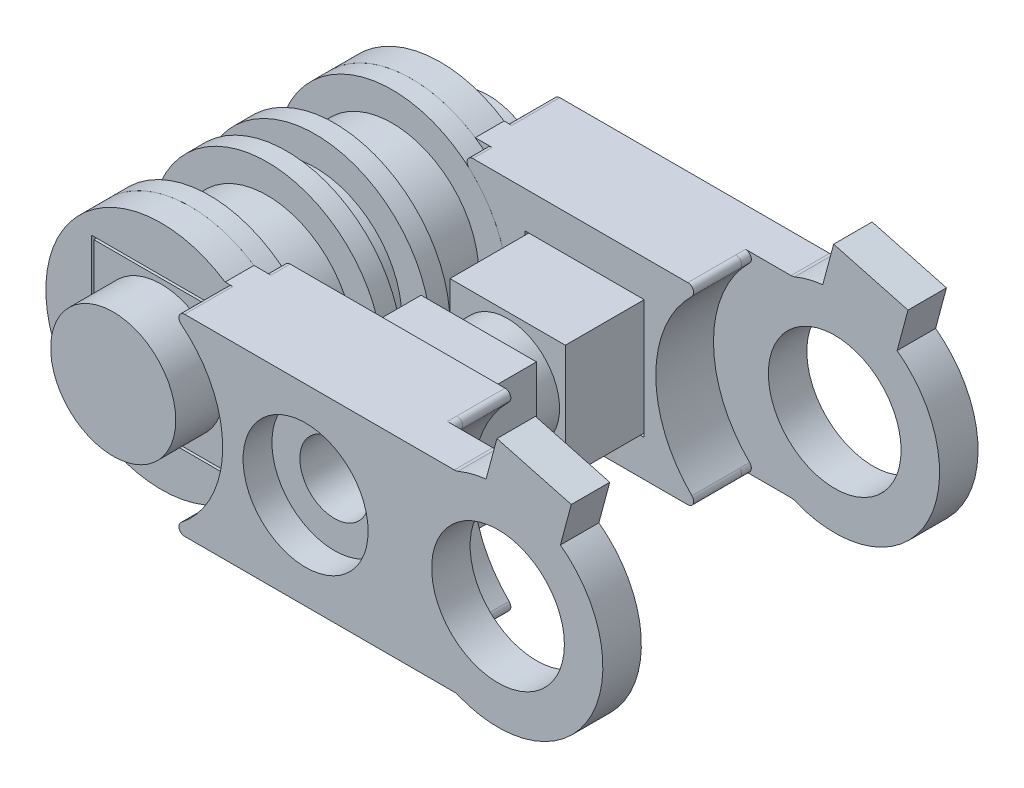
SolidWorks part; units mm, degrees
ref_plane "正面" through (0, 0, 0) normal (0, 0, 1) x (1, 0, 0)
ref_plane "平面" through (0, 0, 0) normal (0, 1, 0) x (1, 0, 0)
ref_plane "右側面" through (0, 0, 0) normal (1, 0, 0) x (0, 0, -1)
sketch "ｽｹｯﾁ1" plane through (0, 0, 0) normal (0, 0, 1) x (1, 0, 0)
  circle A0 centre (0, 0) radius 4.5
  dimension "D1" = 9
extrude "ﾎﾞｽ - 押し出し1" add sketch "ｽｹｯﾁ1" along normal blind 3
sketch "ｽｹｯﾁ2" plane through (0, 0, 0) normal (0, 0, -1) x (-1, 0, 0)
  circle A0 centre (0, 0) radius 6
  dimension "D1" = 12
extrude "ﾎﾞｽ - 押し出し2" add sketch "ｽｹｯﾁ2" along normal blind 1
sketch "ｽｹｯﾁ3" plane through (0, 0, -1) normal (0, 0, -1) x (-1, 0, 0)
  circle A0 centre (0, 0) radius 4.5 construction
  circle A1 centre (0, 0) radius 4.5
extrude "ﾎﾞｽ - 押し出し3" add sketch "ｽｹｯﾁ3" along normal blind 1.5
sketch "ｽｹｯﾁ4" plane through (0, 0, -2.5) normal (0, 0, -1) x (-1, 0, 0)
  circle A1 centre (0, 0) radius 6
  circle A2 centre (0, 0) radius 6
  dimension "D1" = 0
extrude "ﾎﾞｽ - 押し出し4" add sketch "ｽｹｯﾁ4" along normal blind 1
sketch "ｽｹｯﾁ5" plane through (0, 0, -3.5) normal (0, 0, -1) x (-1, 0, 0)
  circle A0 centre (0, 0) radius 4.5 construction
  circle A1 centre (0, 0) radius 4.5
extrude "ﾎﾞｽ - 押し出し5" add sketch "ｽｹｯﾁ5" along normal blind 3
sketch "ｽｹｯﾁ6" plane through (0, 0, -6.5) normal (0, 0, -1) x (-1, 0, 0)
  circle A1 centre (0, 0) radius 6
  circle A2 centre (0, 0) radius 6
  dimension "D1" = 0
extrude "ﾎﾞｽ - 押し出し6" add sketch "ｽｹｯﾁ6" along normal blind 1
sketch "ｽｹｯﾁ7" plane through (0, 0, 3) normal (0, 0, 1) x (1, 0, 0)
  circle A1 centre (0, 0) radius 6
  circle A2 centre (0, 0) radius 6
  dimension "D1" = 0
extrude "ﾎﾞｽ - 押し出し7" add sketch "ｽｹｯﾁ7" along normal blind 1
sketch "ｽｹｯﾁ10" plane through (0, 0, 4) normal (0, 0, 1) x (1, 0, 0)
  line L1 (3.5, -3.5) -> (-3.5, -3.5)
  line L2 (3.5, -3.5) -> (3.5, 3.5)
  line L3 (3.5, 3.5) -> (-3.5, 3.5)
  line L4 (-3.5, -3.5) -> (-3.5, 3.5)
  line L5 (3.5, -3.5) -> (-3.5, 3.5) construction
  line L6 (3.5, 3.5) -> (-3.5, -3.5) construction
  point P0 (0, 0)
  dimension "D1" = 7
  dimension "D2" = 7
extrude "ﾎﾞｽ - 押し出し10" add sketch "ｽｹｯﾁ10" along normal blind 1.5
sketch "ｽｹｯﾁ11" plane through (0, 0, 5.5) normal (0, 0, 1) x (1, 0, 0)
  circle A0 centre (0, 0) radius 3.25
  dimension "D1" = 6.5
extrude "ﾎﾞｽ - 押し出し11" add sketch "ｽｹｯﾁ11" along normal blind 2.5
ref_plane "平面1" through (0, 0, -1.75) normal (0, 0, 1) x (1, 0, 0)
mirror "ﾐﾗｰ1" about plane through (0, 0, -1.75) normal (0, 0, 1) of "ﾎﾞｽ - 押し出し11", "ﾎﾞｽ - 押し出し10"
sketch "ｽｹｯﾁ12" plane through (0, 0, 4) normal (0, 0, 1) x (1, 0, 0)
  line L0 (0, 0) -> (20, 0) construction
  line L1 (3.3166, 5) -> (16.1672, 5)
  line L3 (16.1672, -5) -> (3.3166, -5)
  line L8 (3.64, -3.64) -> (3.64, 3.64)
  line L9 (-3.64, -3.64) -> (3.64, -3.64)
  line L10 (-3.64, 3.64) -> (-3.64, -3.64)
  line L11 (3.64, 3.64) -> (-3.64, 3.64)
  line L12 (3.64, -3.64) -> (3.64, 3.64)
  line L13 (-3.64, -3.64) -> (3.64, -3.64)
  line L14 (-3.64, 3.64) -> (-3.64, -3.64)
  line L15 (3.64, 3.64) -> (-3.64, 3.64)
  circle A0 centre (0, 0) radius 6 construction
  circle A1 centre (20, 0) radius 3.45 construction
  arc A2 (3.3166, 5) -> (3.3166, -5) centre (0, 0) ccw
  circle A3 centre (20, 0) radius 5.45 construction
  circle A4 centre (20, 0) radius 6.3 construction
  arc A5 (16.1672, 5) -> (16.1672, -5) centre (20, 0) ccw
  circle A6 centre (20, 0) radius 6 construction
  circle A7 centre (0, 0) radius 6 construction
  circle A8 centre (20, 0) radius 3.25 construction
  circle A9 centre (0, 0) radius 3.25 construction
  dimension "D3" = 20
  dimension "D6" = 0.3
  dimension "D2" = 5
  dimension "D7" = 5
  dimension "D4" = 0.2
  dimension "D5" = 2
  dimension "D1" = 0.14
extrude "ﾎﾞｽ - 押し出し12" add sketch "ｽｹｯﾁ12" along normal blind 1.5 separate body
sketch "ｽｹｯﾁ13" plane through (0, 0, 5.5) normal (0, 0, 1) x (1, 0, 0)
  line L6 (16.1672, 5) -> (3.3166, 5) construction
  line L9 (16.1672, 5) -> (3.3166, 5) construction
  line L10 (15.3664, 5) -> (3.7135, 5)
  line L11 (15.3664, -5) -> (3.7135, -5)
  circle A1 centre (0, 0) radius 3.25 construction
  arc A7 (16.1672, 5) -> (16.1672, -5) centre (20, 0) ccw construction
  arc A8 (15.577, 4.4864) -> (15.577, -4.4864) centre (20, 0) ccw
  circle A10 centre (0, 0) radius 5.69 construction
  circle A11 centre (0, 0) radius 3.39 construction
  circle A12 centre (0, 0) radius 5.39 construction
  arc A13 (3.5275, 4.4646) -> (3.5275, -4.4646) centre (0, 0) cw
  arc A14 (15.3664, -5) -> (15.577, -4.4864) centre (15.3664, -4.7) ccw
  arc A15 (15.577, 4.4864) -> (15.3664, 5) centre (15.3664, 4.7) ccw
  arc A16 (3.7135, 5) -> (3.5275, 4.4646) centre (3.7135, 4.7) ccw
  arc A17 (3.5275, -4.4646) -> (3.7135, -5) centre (3.7135, -4.7) ccw
  point P24 (2.7159, 5)
  point P29 (2.7159, -5)
  dimension "D1" = 0.14
  dimension "D3" = 0.3
  dimension "D4" = 2
  dimension "D2" = 0.3
extrude "ﾎﾞｽ - 押し出し13" add sketch "ｽｹｯﾁ13" along normal blind 0.5
fillet "ﾌｨﾚｯﾄ9" radius 0.3 2 edges at (16.1672, -5, 4.75) (16.1672, 5, 4.75)
sketch "ｽｹｯﾁ14" plane through (0, 0, 6) normal (0, 0, 1) x (1, 0, 0)
  line L0 (3.7135, 5) -> (17.7301, 5)
  line L3 (3.7135, -5) -> (17.7301, -5)
  arc A0 (17.7301, 5) -> (17.9208, 5.0378) centre (17.7301, 5.5) ccw
  arc A1 (17.7301, -5) -> (17.9208, -5.0378) centre (17.7301, -5.5) cw
  arc A4 (3.5275, -4.4646) -> (3.7135, -5) centre (3.7135, -4.7) ccw construction
  arc A7 (3.5275, -4.4646) -> (3.5275, 4.4646) centre (0, 0) ccw construction
  arc A8 (3.7135, 5) -> (3.5275, 4.4646) centre (3.7135, 4.7) ccw construction
  arc A9 (3.5275, -4.4646) -> (3.7135, -5) centre (3.7135, -4.7) ccw
  arc A10 (3.7135, 5) -> (3.5275, 4.4646) centre (3.7135, 4.7) ccw
  arc A11 (3.5275, -4.4646) -> (3.5275, 4.4646) centre (0, 0) ccw
  circle A12 centre (20, 0) radius 5.45 construction
  arc A13 (17.9208, 5.0378) -> (17.9208, -5.0378) centre (20, 0) cw
  circle A14 centre (20, 0) radius 3.45 construction
  circle A15 centre (20, 0) radius 3.45
  point P19 (17.8315, -5)
  point P22 (17.8315, 5)
  point P24 (17.8315, 5)
  point P27 (17.8315, -5)
  dimension "D1" = 0.5
extrude "ﾎﾞｽ - 押し出し14" add sketch "ｽｹｯﾁ14" along normal blind 2
sketch "ｽｹｯﾁ15" plane through (0, 0, 4) normal (0, 0, -1) x (-1, 0, 0)
  line L0 (-15.3664, 5) -> (-4.1952, 5)
  line L1 (-3.3166, 5) -> (-16.1672, 5) construction
  line L2 (-15.3664, -5) -> (-4.1952, -5)
  line L3 (-16.1672, -5) -> (-3.3166, -5) construction
  circle A2 centre (0, 0) radius 6 construction
  arc A3 (-3.9955, 4.4762) -> (-3.9955, -4.4762) centre (0, 0) ccw
  arc A7 (-4.1952, -5) -> (-3.9955, -4.4762) centre (-4.1952, -4.7) ccw
  arc A8 (-4.1952, 5) -> (-3.9955, 4.4762) centre (-4.1952, 4.7) cw
  arc A10 (-15.577, -4.4864) -> (-15.3664, -5) centre (-15.3664, -4.7) ccw construction
  arc A11 (-15.577, -4.4864) -> (-15.577, 4.4864) centre (-20, 0) ccw construction
  arc A12 (-15.3664, 5) -> (-15.577, 4.4864) centre (-15.3664, 4.7) ccw construction
  arc A13 (-15.577, -4.4864) -> (-15.3664, -5) centre (-15.3664, -4.7) ccw
  arc A14 (-15.577, -4.4864) -> (-15.577, 4.4864) centre (-20, 0) ccw
  arc A15 (-15.3664, 5) -> (-15.577, 4.4864) centre (-15.3664, 4.7) ccw
  point P26 (-3.3166, -5)
  point P29 (-3.3166, 5)
  dimension "D2" = 0.3
extrude "ﾎﾞｽ - 押し出し15" add sketch "ｽｹｯﾁ15" along normal blind 1
mirror "ﾐﾗｰ2" about plane through (0, 0, -1.75) normal (0, 0, 1) of bodies 116
sketch "ｽｹｯﾁ16" plane through (0, 0, 8) normal (0, 0, 1) x (1, 0, 0)
  line L0 (0, 0) -> (20, 0) construction
  circle A0 centre (20, 0) radius 3.45 construction
  circle A1 centre (10, 0) radius 1.8
  dimension "D1" = 3.6
extrude "ｶｯﾄ - 押し出し1" cut sketch "ｽｹｯﾁ16" against normal through all
sketch "ｽｹｯﾁ17" plane through (0, 0, -6.5) normal (0, 0, 1) x (1, 0, 0)
  line L1 (13.1, -3.1) -> (6.9, -3.1)
  line L2 (13.1, -3.1) -> (13.1, 3.1)
  line L3 (13.1, 3.1) -> (6.9, 3.1)
  line L4 (6.9, -3.1) -> (6.9, 3.1)
  line L5 (13.1, -3.1) -> (6.9, 3.1) construction
  line L6 (13.1, 3.1) -> (6.9, -3.1) construction
  point P0 (10, 0)
  dimension "D2" = 6.2
  dimension "D1" = 6.2
extrude "ｶｯﾄ - 押し出し2" cut sketch "ｽｹｯﾁ17" against normal blind 2
sketch "ｽｹｯﾁ18" plane through (0, 0, 3) normal (0, 0, -1) x (-1, 0, 0)
  line L0 (-7, 3) -> (-13, 3)
  line L5 (-13, 3) -> (-13, -3)
  line L6 (-13, -3) -> (-7, -3)
  line L7 (-7, -3) -> (-7, 3)
  line L8 (-13.1, -3.1) -> (-6.9, -3.1)
  line L9 (-6.9, -3.1) -> (-6.9, 3.1)
  line L10 (-6.9, 3.1) -> (-13.1, 3.1)
  line L11 (-13.1, 3.1) -> (-13.1, -3.1)
  line L12 (-13.1, -3.1) -> (-6.9, -3.1) construction
  line L13 (-6.9, -3.1) -> (-6.9, 3.1) construction
  line L14 (-6.9, 3.1) -> (-13.1, 3.1) construction
  line L15 (-13.1, 3.1) -> (-13.1, -3.1) construction
  dimension "D1" = 0
  dimension "D2" = 0.1
extrude "ﾎﾞｽ - 押し出し16" add sketch "ｽｹｯﾁ18" along normal up to surface (11.5 mm away) up to face at (10, 0, -8.5)
sketch "ｽｹｯﾁ19" plane through (0, 0, 3) normal (0, 0, 1) x (1, 0, 0)
  circle A0 centre (10, 0) radius 1.8 construction
  circle A1 centre (10, 0) radius 1.8
extrude "ｶｯﾄ - 押し出し3" cut sketch "ｽｹｯﾁ19" against normal through all
sketch "ｽｹｯﾁ20" plane through (0, 0, -1.75) normal (0, 0, 1) x (1, 0, 0)
  line L4 (13, 3) -> (7, 3)
  line L5 (13, -3) -> (13, 3)
  line L6 (7, -3) -> (13, -3)
  line L7 (7, 3) -> (7, -3)
  line L8 (13, 3) -> (7, 3)
  line L9 (13, -3) -> (13, 3)
  line L10 (7, -3) -> (13, -3)
  line L11 (7, 3) -> (7, -3)
  circle A1 centre (10, 0) radius 2.7
  dimension "D2" = 5.4
  dimension "D1" = 0
extrude "ｶｯﾄ - 押し出し4" cut sketch "ｽｹｯﾁ20" against normal blind 0.75 and the other way blind 0.75
sketch "ｽｹｯﾁ21" plane through (0, 0, 8) normal (0, 0, 1) x (1, 0, 0)
  circle A0 centre (10, 0) radius 3.25
  dimension "D1" = 6.5
extrude "ｶｯﾄ - 押し出し5" cut sketch "ｽｹｯﾁ21" against normal blind 1.5
sketch "ｽｹｯﾁ22" plane through (0, 0, -11.5) normal (0, 0, -1) x (-1, 0, 0)
  line L1 (-11.6743, 2.9) -> (-13.3486, 0)
  line L2 (-13.3486, 0) -> (-11.6743, -2.9)
  line L3 (-11.6743, -2.9) -> (-8.3257, -2.9)
  line L4 (-8.3257, -2.9) -> (-6.6514, 0)
  line L5 (-6.6514, 0) -> (-8.3257, 2.9)
  line L6 (-8.3257, 2.9) -> (-11.6743, 2.9)
  circle A0 centre (-10, 0) radius 2.9 construction
  dimension "D1" = 5.8
extrude "ｶｯﾄ - 押し出し6" cut sketch "ｽｹｯﾁ22" against normal blind 1
sketch "ｽｹｯﾁ23" plane through (0, 0, 8) normal (0, 0, 1) x (1, 0, 0)
  line L0 (20, 0) -> (21.4106, 5.2643) construction
  line L1 (19.0128, 4.0433) -> (22.8765, 3.008)
  line L2 (19.0128, 4.0433) -> (19.9446, 7.5206)
  line L3 (19.9446, 7.5206) -> (23.8083, 6.4853)
  line L4 (22.8765, 3.008) -> (23.8083, 6.4853)
  line L5 (19.0128, 4.0433) -> (23.8083, 6.4853) construction
  line L6 (19.9446, 7.5206) -> (22.8765, 3.008) construction
  line L7 (20, 0) -> (20, 5.45) construction
  arc A0 (17.9208, -5.0378) -> (17.9208, 5.0378) centre (20, 0) ccw construction
  point P0 (21.4106, 5.2643)
  dimension "D1" = 1.8
  dimension "D2" = 4
  dimension "D3" = 15
extrude "ﾎﾞｽ - 押し出し17" add sketch "ｽｹｯﾁ23" against normal up to surface (2 mm away) up to face at (17.3986, 0, 6)
sketch "ｽｹｯﾁ24" plane through (0, 0, -11.5) normal (0, 0, -1) x (-1, 0, 0)
  line L4 (-22.8765, 3.008) -> (-19.0128, 4.0433)
  line L5 (-23.8083, 6.4853) -> (-22.8765, 3.008)
  line L6 (-19.9446, 7.5206) -> (-23.8083, 6.4853)
  line L7 (-19.0128, 4.0433) -> (-19.9446, 7.5206)
  line L8 (-22.8765, 3.008) -> (-19.0128, 4.0433)
  line L9 (-23.8083, 6.4853) -> (-22.8765, 3.008)
  line L10 (-19.9446, 7.5206) -> (-23.8083, 6.4853)
  line L11 (-19.0128, 4.0433) -> (-19.9446, 7.5206)
  dimension "D1" = 0
extrude "ﾎﾞｽ - 押し出し18" add sketch "ｽｹｯﾁ24" against normal up to surface (2 mm away) up to face at (17.3986, 0, -9.5)
equation "\"D7@ｽｹｯﾁ12\"=\"D2@ｽｹｯﾁ12\""
equation "\"D1@ｽｹｯﾁ17\"=\"D2@ｽｹｯﾁ17\""
